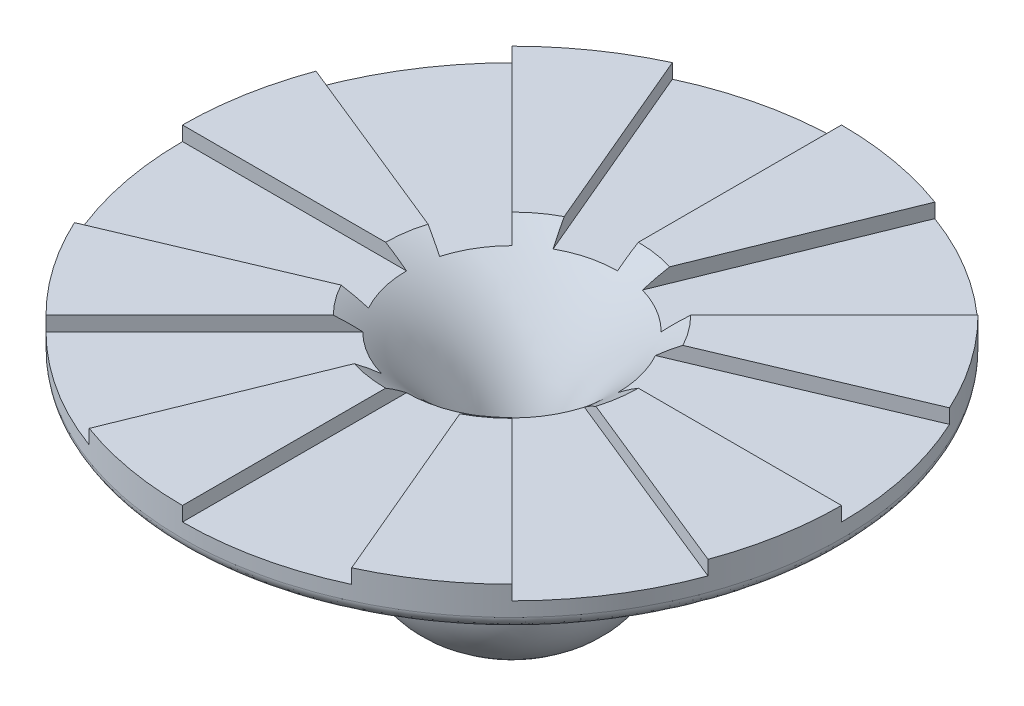
SolidWorks part; units mm, degrees
material "Melamine resin"
ref_plane "Front Plane" through (0, 0, 0) normal (0, 0, 1) x (1, 0, 0)
ref_plane "Top Plane" through (0, 0, 0) normal (0, 1, 0) x (1, 0, 0)
ref_plane "Right Plane" through (0, 0, 0) normal (1, 0, 0) x (0, 0, -1)
sketch "Sketch2" plane through (0, 0, 0) normal (0, 0, 1) x (1, 0, 0)
  line L1 (-10.46, 0) -> (-10.46, -2)
  line L4 (-3, -6) -> (0, -6) construction
  line L6 (-7, -2) -> (-10.46, -2)
  line L9 (-3, -6) -> (-7, -6) construction
  line L10 (-7, -2) -> (-7, -6) construction
  line L12 (1, -6) -> (1, 0.6031)
  line L13 (-10.46, 0) -> (-3.3944, 0)
  line L14 (0, -6) -> (0, -9)
  line L15 (0, -9) -> (1, -9)
  line L16 (1, -9) -> (1, -6)
  line L17 (1, -6) -> (0, -6)
  arc A0 (-3, -6) -> (-7, -2) centre (-7, -6) ccw
  arc A1 (-3, -6) -> (0, -9) centre (0, -6) ccw
  arc A2 (-3.3944, 0) -> (0, -6) centre (-7, -6) cw
  dimension "D1" = 11.46
  dimension "D2" = 2
  dimension "D4" = 3
  dimension "D5" = 4
  dimension "D6" = 1
revolve "Revolve4" add sketch "Sketch2" angle 360 about L16
fillet "Fillet3" radius 1 1 edges at (1, -2, -11.46)
sketch "Sketch8" plane through (0, 0, 0) normal (0, 1, 0) x (1, 0, 0)
  line L4 (0, 0) -> (18.2558, 0)
  line L5 (0, 0) -> (16.5861, 7.0143)
  line L6 (16.5861, 7.0143) -> (18.2558, 0)
extrude "Cut-Extrude5" cut sketch "Sketch8" against normal blind 0.5
pattern_circular "CirPattern3" count 8 over 360 about axis through (1, 0, 0) along (0, 1, 0) of "Cut-Extrude5"
